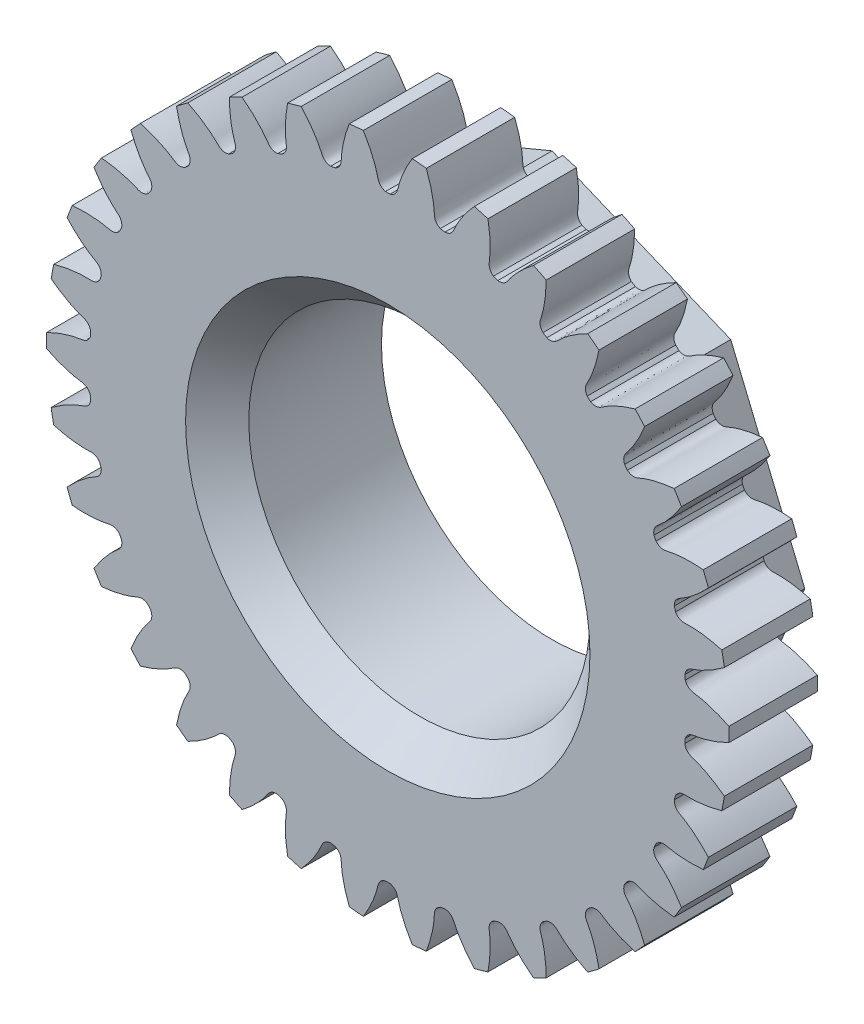
SolidWorks part; units mm, degrees
material "ABS"
ref_plane "前视基准面" through (0, 0, 0) normal (0, 0, 1) x (1, 0, 0)
ref_plane "上视基准面" through (0, 0, 0) normal (0, 1, 0) x (1, 0, 0)
ref_plane "右视基准面" through (0, 0, 0) normal (1, 0, 0) x (0, 0, -1)
sketch "草图1" plane through (0, 0, 0) normal (0, 0, 1) x (1, 0, 0)
  circle A0 centre (0, 0) radius 27
extrude "凸台-拉伸1" add sketch "草图1" along normal blind 7
ref_axis "基准轴1" through (0, 0, -1.5) along (0, 0, 1)
sketch "草图2" plane through (0, 0, 0) normal (0, 0, 1) x (1, 0, 0)
  line L0 (0, 0) -> (0, 27) construction
  circle A0 centre (0, 0) radius 27 construction
  arc A1 (0.1832, 23.6243) -> (-0.1832, 23.6243) centre (0, 0) ccw
  arc A2 (5.0574, 30.5549) -> (-5.0574, 30.5549) centre (0, 0) ccw
  spline S0 degree 3 poles (0.1832, 23.6243) (0.7166, 23.7751) (0.7634, 24.1888) (0.8799, 24.6236) (0.9129, 24.7382) (0.9511, 24.8613) (0.9947, 24.9927) (1.0441, 25.1322) (1.0997, 25.2797) (1.1618, 25.4349) (1.2307, 25.5977) (1.3068, 25.7679) (1.3903, 25.9451) (1.4816, 26.1292) (1.581, 26.32) (1.6888, 26.5172) (1.8053, 26.7204) (1.9308, 26.9296) (2.0655, 27.1443) (2.2097, 27.3642) (2.3637, 27.5892) (2.5278, 27.8188) (2.7021, 28.0528) (2.887, 28.2909) (3.0826, 28.5326) (3.2892, 28.7777) (3.5069, 29.0258) (3.7361, 29.2767) (3.9768, 29.5298) (4.2293, 29.7848) (4.5864, 30.1315) (4.8656, 30.3865) (5.0574, 30.5549) knots 0 0 0 0 0.130724 0.143504 0.157401 0.172415 0.188546 0.205794 0.224159 0.243641 0.26424 0.285956 0.308788 0.332738 0.357805 0.383988 0.411289 0.439706 0.46924 0.499892 0.53166 0.564545 0.598547 0.633666 0.669902 0.707255 0.745725 0.785312 0.826016 0.867836 0.910774 1 1 1 1
  spline S1 degree 3 poles (-0.1832, 23.6243) (-0.7166, 23.7751) (-0.7634, 24.1888) (-0.8799, 24.6236) (-0.9129, 24.7382) (-0.9511, 24.8613) (-0.9947, 24.9927) (-1.0441, 25.1322) (-1.0997, 25.2797) (-1.1618, 25.4349) (-1.2307, 25.5977) (-1.3068, 25.7679) (-1.3903, 25.9451) (-1.4816, 26.1292) (-1.581, 26.32) (-1.6888, 26.5172) (-1.8053, 26.7204) (-1.9308, 26.9296) (-2.0655, 27.1443) (-2.2097, 27.3642) (-2.3637, 27.5892) (-2.5278, 27.8188) (-2.7021, 28.0528) (-2.887, 28.2909) (-3.0826, 28.5326) (-3.2892, 28.7777) (-3.5069, 29.0258) (-3.7361, 29.2767) (-3.9768, 29.5298) (-4.2293, 29.7848) (-4.5864, 30.1315) (-4.8656, 30.3865) (-5.0574, 30.5549) knots 0 0 0 0 0.130724 0.143504 0.157401 0.172415 0.188546 0.205794 0.224159 0.243641 0.26424 0.285956 0.308788 0.332738 0.357805 0.383988 0.411289 0.439706 0.46924 0.499892 0.53166 0.564545 0.598547 0.633666 0.669902 0.707255 0.745725 0.785312 0.826016 0.867836 0.910774 1 1 1 1
extrude "切除-拉伸1" cut sketch "草图2" along normal through all
pattern_circular "阵列(圆周)1" count 34 every 10.588 about axis through (0, 0, -1.5) along (0, 0, 1) of "切除-拉伸1"
sketch "草图3" plane through (0, 0, 0) normal (0, 0, 1) x (1, 0, 0)
  circle A0 centre (0, 0) radius 25.5 construction
  dimension "Dn" = 51
sketch "草图4" plane through (0, 0, 7) normal (0, 0, 1) x (1, 0, 0)
  circle A0 centre (0, 0) radius 13.5
  dimension "D1" = 27
extrude "切除-拉伸2" cut sketch "草图4" against normal through all
chamfer "倒角1" distance 2.5 angle 45 1 edges at (13.5, 0, 7)
sketch "草图5" plane through (0, 0, 7) normal (0, 0, 1) x (1, 0, 0)
  line L0 (-14.1421, 14.1421) -> (-20, 0)
  line L1 (-20, 0) -> (-14.1421, -14.1421)
  line L2 (-14.1421, -14.1421) -> (0, -20)
  line L3 (0, -20) -> (14.1421, -14.1421)
  line L4 (14.1421, -14.1421) -> (20, 0)
  line L5 (20, 0) -> (14.1421, 14.1421)
  line L6 (14.1421, 14.1421) -> (0, 20)
  line L7 (0, 20) -> (-14.1421, 14.1421)
  circle A0 centre (0, 0) radius 13.5
  circle A1 centre (0, 0) radius 20 construction
  dimension "D1" = 27
  dimension "D2" = 40
extrude "凸台-拉伸2" add sketch "草图5" against normal blind 6 from surface starting at face at (13.5, 0, 0)
